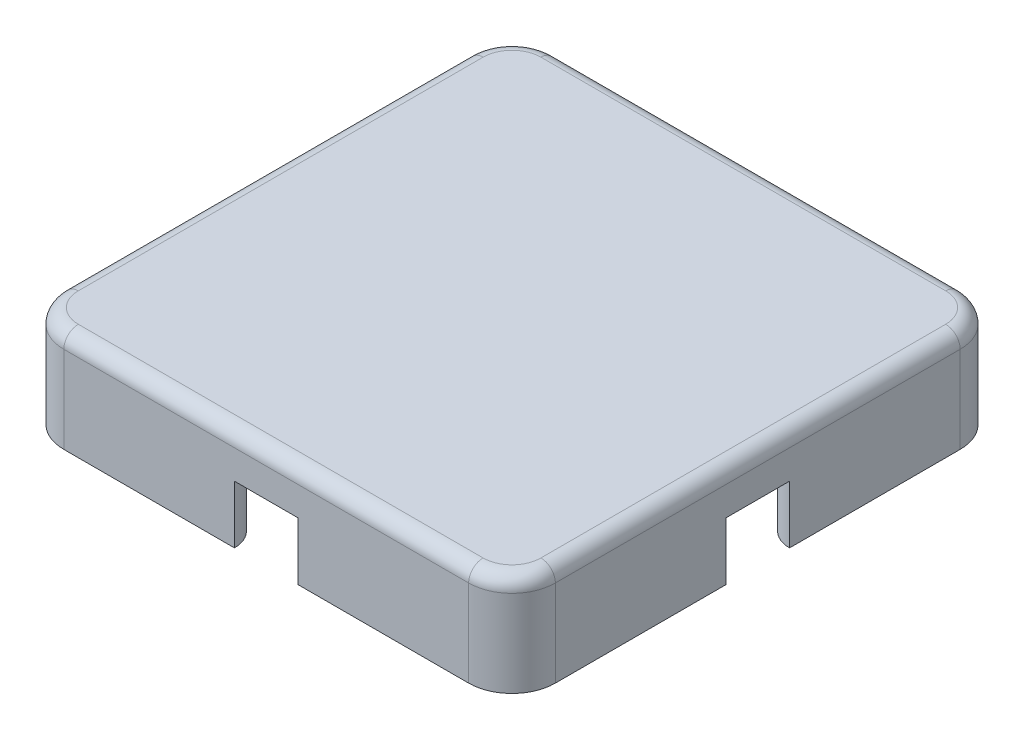
SolidWorks part; units mm, degrees
material "TPU 98A"
ref_plane "Front Plane" through (0, 0, 0) normal (0, 0, 1) x (1, 0, 0)
ref_plane "Top Plane" through (0, 0, 0) normal (0, 1, 0) x (1, 0, 0)
ref_plane "Right Plane" through (0, 0, 0) normal (1, 0, 0) x (0, 0, -1)
sketch "Sketch1" plane through (0, 0, 0) normal (0, 1, 0) x (1, 0, 0)
  line L1 (-14, -17) -> (14, -17)
  line L2 (-17, -14) -> (-17, 14)
  line L3 (-14, 17) -> (14, 17)
  line L4 (17, -14) -> (17, 14)
  line L5 (-17, -17) -> (17, 17) construction
  line L6 (-17, 17) -> (17, -17) construction
  arc A0 (-14, -17) -> (-17, -14) centre (-14, -14) cw
  arc A1 (14, -17) -> (17, -14) centre (14, -14) ccw
  arc A2 (14, 17) -> (17, 14) centre (14, 14) cw
  arc A3 (-17, 14) -> (-14, 17) centre (-14, 14) cw
  point P0 (0, 0)
  dimension "D2" = 3
  dimension "D1" = 34
extrude "Boss-Extrude1" add sketch "Sketch1" along normal blind 7
shell "Shell1" thickness 2 removed face at (0, 0, 0)
fillet "Fillet1" radius 1 8 edges at (-17, 7, 0) (-16.1213, 7, -16.1213) (0, 7, -17) (16.1213, 7, -16.1213) (17, 7, 0) (16.1213, 7, 16.1213) (0, 7, 17) (-16.1213, 7, 16.1213)
sketch "Sketch2" plane through (0, 5, 0) normal (0, -1, 0) x (1, 0, 0)
  circle A0 centre (0, 0) radius 8.5
  dimension "D1" = 17
extrude "Boss-Extrude2" add sketch "Sketch2" along normal blind 1.6
sketch "Sketch3" plane through (0, 0, 0) normal (0, -1, 0) x (1, 0, 0)
  line L0 (0, 17) -> (0, -17) construction
  line L1 (-14, 17) -> (14, 17) construction
  line L2 (14, -17) -> (-14, -17) construction
  line L3 (-17, 0) -> (17, 0) construction
  line L4 (-17, -14) -> (-17, 14) construction
  line L5 (17, 14) -> (17, -14) construction
  line L6 (-2.2, 17) -> (-2.2, 15)
  line L7 (-17, -2.2) -> (-15, -2.2)
  line L8 (2.2, 17) -> (2.2, 15)
  line L9 (-17, 2.2) -> (-15, 2.2)
  line L10 (14, -15) -> (-14, -15) construction
  line L11 (-15, -14) -> (-15, 14) construction
  line L12 (-14, 15) -> (14, 15) construction
  line L13 (15, 14) -> (15, -14) construction
  line L14 (2.2, -15) -> (-2.2, -15)
  line L15 (-15, -2.2) -> (-15, 2.2)
  line L16 (-2.2, 15) -> (2.2, 15)
  line L17 (15, 2.2) -> (15, -2.2)
  line L18 (15, 2.2) -> (17, 2.2)
  line L19 (2.2, 17) -> (2.2, -17) construction
  line L20 (2.2, -17) -> (-2.2, -17)
  line L21 (-2.2, 17) -> (-2.2, -17) construction
  line L22 (2.2, -15) -> (2.2, -17)
  line L23 (-2.2, -15) -> (-2.2, -17)
  line L24 (-17, 2.2) -> (17, 2.2) construction
  line L25 (15, -2.2) -> (17, -2.2)
  line L26 (-17, -2.2) -> (17, -2.2) construction
  line L27 (-17, -2.2) -> (-17, 2.2)
  line L28 (-2.2, 17) -> (2.2, 17)
  line L29 (17, 2.2) -> (17, -2.2)
  dimension "D1" = 2.2
  dimension "D2" = 2.2
extrude "Cut-Extrude1" cut sketch "Sketch3" against normal blind 4
fillet "Fillet2" radius 2 8 edges at (-15, 2, -2.2) (-15, 2, 2.2) (-2.2, 2, 15) (2.2, 2, 15) (15, 2, 2.2) (15, 2, -2.2) (2.2, 2, -15) (-2.2, 2, -15)
equation "\"D1@Sketch3\"=\"D2@Sketch3\""
